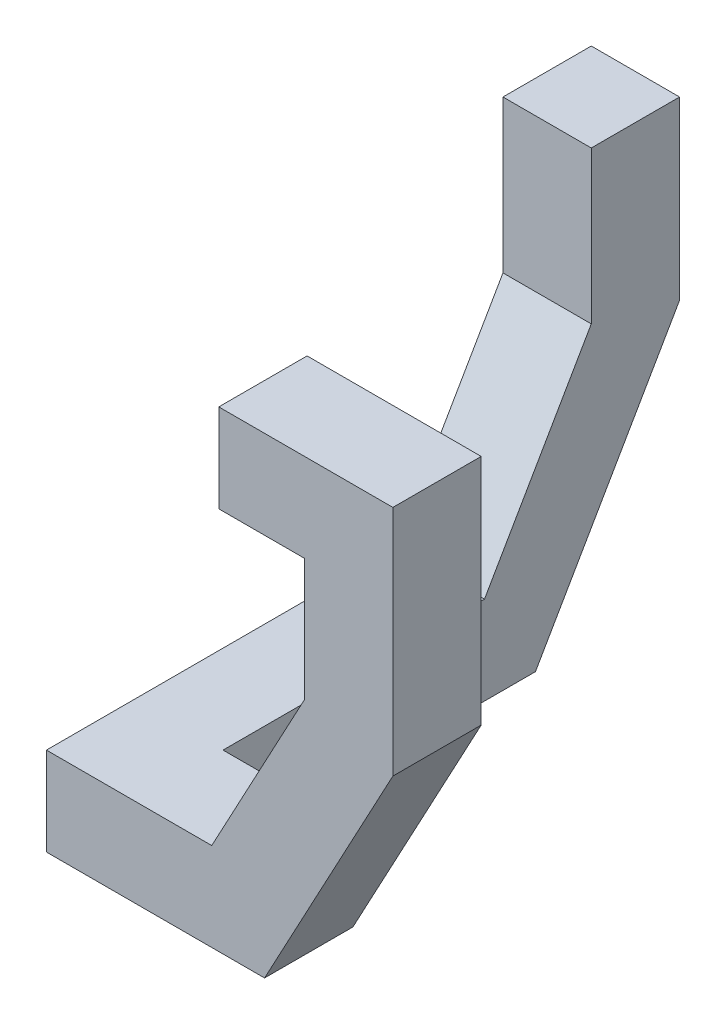
SolidWorks part; units mm, degrees
ref_plane "Front Plane" through (0, 0, 0) normal (0, 0, 1) x (1, 0, 0)
ref_plane "Top Plane" through (0, 0, 0) normal (0, 1, 0) x (1, 0, 0)
ref_plane "Right Plane" through (0, 0, 0) normal (1, 0, 0) x (0, 0, -1)
ref_axis "Z" through (0, 0, 32.3921) along (0, 0, -1)
sketch "Sketch1" plane through (0, 0, 0) normal (1, 0, 0) x (0, 0, -1)
  line L0 (-5, 2.3974) -> (0, 2.3974)
  line L1 (0, 2.3974) -> (0, -7.5684)
  line L2 (0, -7.5684) -> (-8.1602, -21.7022)
  line L3 (-8.1602, -21.7022) -> (-25.8497, -21.7022)
  line L4 (-25.8497, -21.7022) -> (-25.8497, -16.7022)
  line L5 (-25.8497, -16.7022) -> (-11.0469, -16.7022)
  line L6 (-11.0469, -16.7022) -> (-5, -6.2286)
  line L7 (-5, -6.2286) -> (-5, 2.3974)
  line L8 (-9.0657, -13.2706) -> (-4.7356, -15.7706) construction
  point P10 (-12.4478, -15.7143)
  point P12 (0, 0)
  dimension "D1" = 5
extrude "Boss-Extrude1" add sketch "Sketch1" along normal blind 2.5 and the other way blind 2.5
sketch "Sketch2" plane through (0, 0, 25.8497) normal (0, 0, 1) x (1, 0, 0)
  line L0 (5, -16.7022) -> (6.8604, -16.7022)
  line L1 (6.8604, -16.7022) -> (12.1164, -6.9117)
  line L2 (12.1164, -6.9117) -> (12.1164, 0.0061)
  line L3 (12.1164, 0.0061) -> (7.2596, 0.0061)
  line L4 (7.2596, 0.0061) -> (7.2596, 5.0061)
  line L5 (7.2596, 5.0061) -> (17.1164, 5.0061)
  line L6 (17.1164, 5.0061) -> (17.1164, -8.1689)
  line L7 (17.1164, -8.1689) -> (9.8511, -21.7022)
  line L8 (9.8511, -21.7022) -> (5, -21.7022)
  line L9 (5, -21.7022) -> (-2.5, -21.7022)
  line L10 (-2.5, -21.7022) -> (-2.5, -16.7022)
  line L11 (-2.5, -16.7022) -> (5, -16.7022)
  line L12 (2.5, -16.7022) -> (-2.5, -16.7022) construction
  line L13 (2.5, -21.7022) -> (-2.5, -21.7022) construction
  line L14 (-2.5, -16.7022) -> (-2.5, -21.7022) construction
  line L15 (10.1846, -10.5101) -> (14.5899, -12.8751) construction
  line L16 (12.1164, 0.0061) -> (17.1164, 0.0061) construction
  point P18 (0, 0)
  point P19 (11.1886, -0.7981)
  point P20 (6.3591, -2.6038)
  point P21 (6.7154, 2.726)
  point P24 (15.1583, -13.1802)
  point P25 (12.1164, -6.9117)
  point P26 (7.2596, 0.0061)
extrude "Boss-Extrude2" add sketch "Sketch2" along normal blind 5
equation "\"rbracket-width\" = 5"
equation "\"D1@Boss-Extrude1\"=\"rbracket-width\"/2"
equation "\"D2@Boss-Extrude1\"=\"rbracket-width\"/2"
